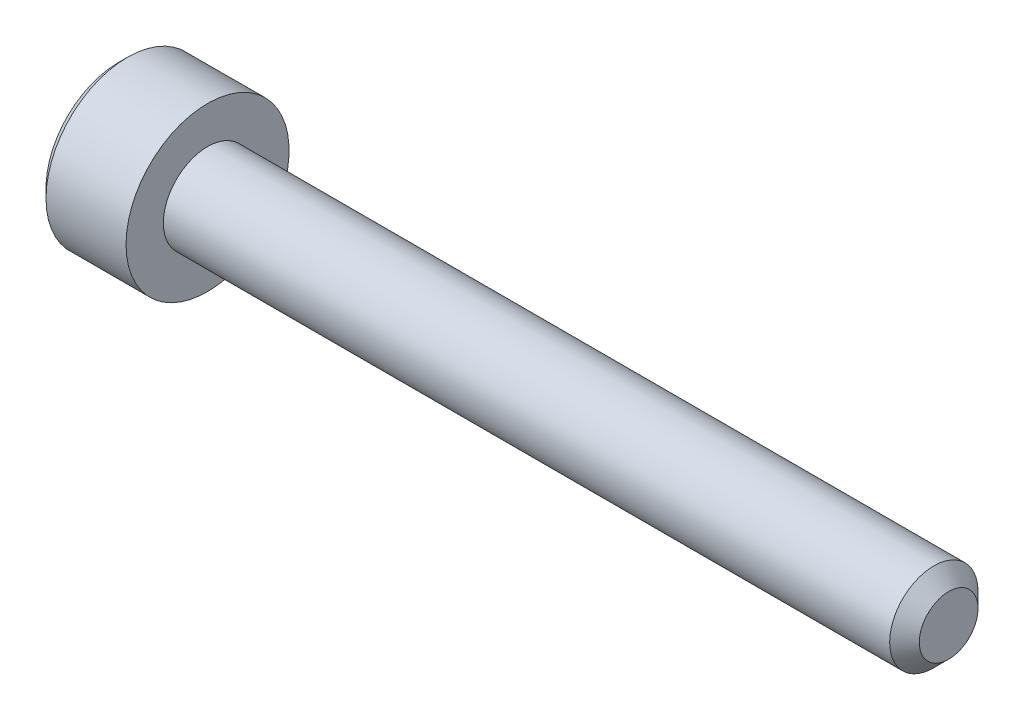
SolidWorks part; units mm, degrees
material "AISI Type 316L stainless steel"
ref_plane "Front Plane" through (0, 0, 0) normal (0, 0, 1) x (1, 0, 0)
ref_plane "Top Plane" through (0, 0, 0) normal (0, 1, 0) x (1, 0, 0)
ref_plane "Right Plane" through (0, 0, 0) normal (1, 0, 0) x (0, 0, -1)
sketch "Sketch1" plane through (0, 0, 0) normal (0, 0, 1) x (1, 0, 0)
  line L0 (-88.7055, 0) -> (96.9812, 0) construction
  line L1 (0, 0) -> (0, 2.75)
  line L2 (0, 2.75) -> (3, 2.75)
  line L4 (28, 0) -> (28, 1.49)
  line L5 (28, 1.49) -> (3, 1.49)
  line L6 (3, 1.49) -> (3, 2.75)
  line L7 (0, 0) -> (28, 0)
  dimension "D1" = 25
  dimension "D2" = 3
  dimension "D3" = 1.49
  dimension "D4" = 2.75
revolve "Revolve1" add sketch "Sketch1" angle 360 about L0
chamfer "Chamfer1" distance 0.5 angle 45 1 edges at (28, 0, 1.49)
chamfer "Chamfer2" distance 0.3 angle 45 1 edges at (0, 0, 2.75)
sketch "Sketch3" plane through (0, 0, 0) normal (1, 0, 0) x (0, 0, -1)
  line L1 (-1.4434, 0) -> (-0.7217, -1.25)
  line L2 (-0.7217, -1.25) -> (0.7217, -1.25)
  line L3 (0.7217, -1.25) -> (1.4434, 0)
  line L4 (1.4434, 0) -> (0.7217, 1.25)
  line L5 (0.7217, 1.25) -> (-0.7217, 1.25)
  line L6 (-0.7217, 1.25) -> (-1.4434, 0)
  circle A0 centre (0, 0) radius 1.25 construction
extrude "Cut-Extrude1" cut sketch "Sketch3" along normal blind 2.5
chamfer "Chamfer3" distance 0.3 angle 45 6 edges at (0, 1.25, 0) (0, 0.625, 1.0825) (0, -0.625, 1.0825) (0, -1.25, 0) (0, -0.625, -1.0825) (0, 0.625, -1.0825)
sketch "Sketch5" plane through (28, 0, 0) normal (1, 0, 0) x (0, 0, -1)
  circle A0 centre (0, 0) radius 1.49
curve "Helix/Spiral1" pitch 0.5 height 20 turns 40
sketch "Sketch8" plane through (0, 0, 0) normal (0, 1, 0) x (1, 0, 0)
  line L0 (28, 1.49) -> (28, 1.1111) construction
  line L1 (28.0625, 1.2194) -> (28.3281, 1.6794)
  line L2 (28.3281, 1.6794) -> (27.6719, 1.6794)
  line L3 (27.6719, 1.6794) -> (27.9375, 1.2194)
  line L4 (28, -0.99) -> (28, 0.99) construction
  circle A0 centre (28, 1.49) radius 0.1894 construction
  arc A1 (28.0625, 1.2194) -> (27.9375, 1.2194) centre (28, 1.2555) cw
  dimension "D2" = 0.0722
  dimension "D1" = 0.3789
sweep "Cut-Sweep1" [suppressed] cut profiles "Sketch8" path "Helix/Spiral1"
